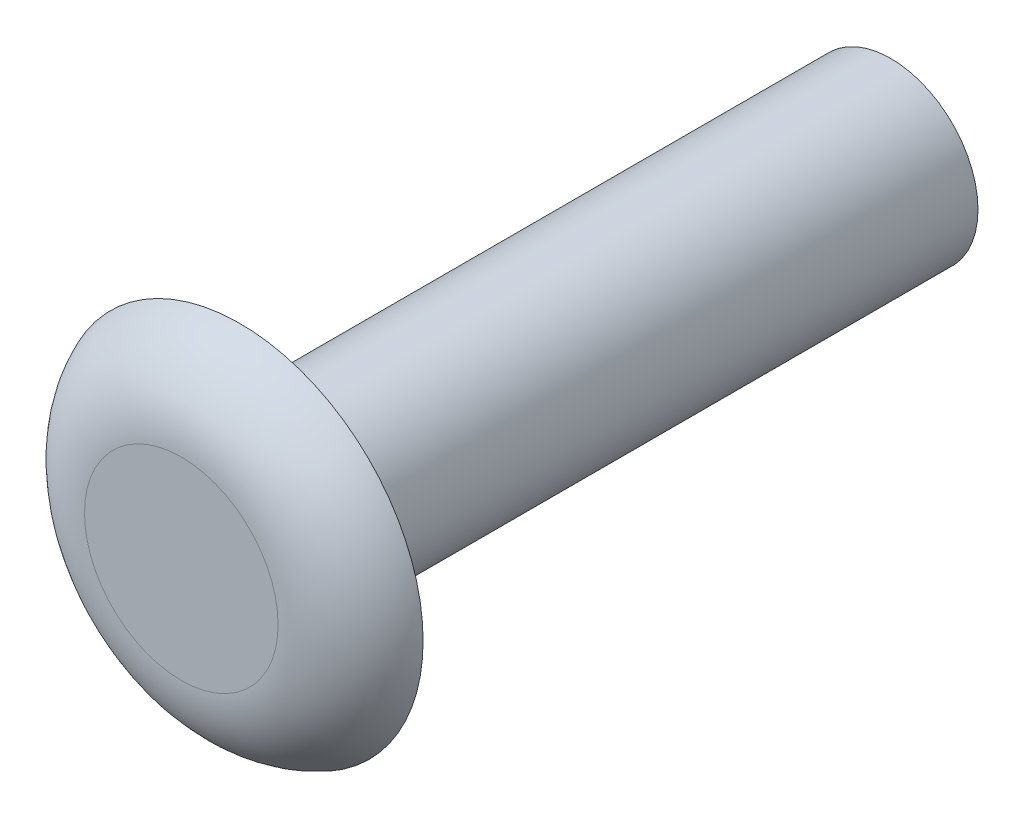
SolidWorks part; units mm, degrees
material "6061 Alloy"
ref_plane "Front Plane" through (0, 0, 0) normal (0, 0, 1) x (1, 0, 0)
ref_plane "Top Plane" through (0, 0, 0) normal (0, 1, 0) x (1, 0, 0)
ref_plane "Right Plane" through (0, 0, 0) normal (1, 0, 0) x (0, 0, -1)
sketch "Sketch1" plane through (0, 0, 0) normal (0, 0, 1) x (1, 0, 0)
  circle A0 centre (0, 0) radius 5.0038
  dimension "D1" = 10.0076
extrude "Boss-Extrude1" add sketch "Sketch1" along normal blind 1.6002
sketch "Sketch2" plane through (0, 0, 0) normal (0, 0, 1) x (1, 0, 0)
  circle A0 centre (0, 0) radius 2.3813
  dimension "D1" = 4.7625
extrude "Boss-Extrude2" add sketch "Sketch2" against normal blind 17.78
fillet "Fillet1" radius 2.54 1 edges at (5.0038, 0, 1.6002)
